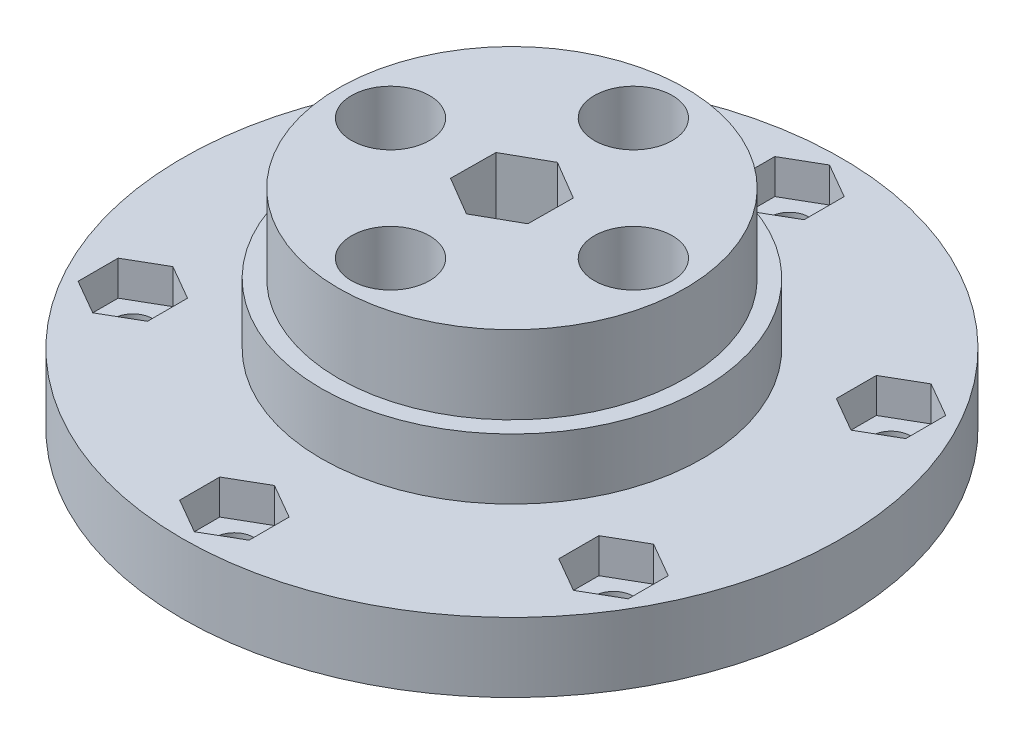
SolidWorks part; units mm, degrees
ref_plane "Спереди" through (0, 0, 0) normal (0, 0, 1) x (1, 0, 0)
ref_plane "Сверху" through (0, 0, 0) normal (0, 1, 0) x (1, 0, 0)
ref_plane "Справа" through (0, 0, 0) normal (1, 0, 0) x (0, 0, -1)
sketch "Эскиз1" plane through (0, 0, 0) normal (0, 1, 0) x (1, 0, 0)
  circle A0 centre (0, 0) radius 38
  dimension "D1" = 76
extrude "Бобышка-Вытянуть1" add sketch "Эскиз1" along normal blind 8
sketch "Эскиз2" plane through (0, 8, 0) normal (0, 1, 0) x (1, 0, 0)
  circle A0 centre (0, 0) radius 20
  dimension "D1" = 40
extrude "Бобышка-Вытянуть2" add sketch "Эскиз2" along normal blind 16
sketch "Эскиз7" plane through (0, 8, 0) normal (0, 1, 0) x (1, 0, 0)
  circle A0 centre (0, 0) radius 22
  dimension "D1" = 44
extrude "Бобышка-Вытянуть3" add sketch "Эскиз7" along normal blind 7
sketch "Эскиз3" plane through (0, 24, 0) normal (0, 1, 0) x (1, 0, 0)
  circle A0 centre (0, 14) radius 4.5
  circle A1 centre (14, 0) radius 4.5
  circle A2 centre (0, -14) radius 4.5
  circle A3 centre (-14, 0) radius 4.5
  circle A4 centre (0, 0) radius 3.25
  point P12 (0, 0)
  dimension "D2" = 9
  dimension "D4" = 6.5
  dimension "D1" = 14
  dimension "D3" = 4
extrude "Вырез-Вытянуть1" cut sketch "Эскиз3" against normal through all
sketch "Эскиз4" plane through (0, 24, 0) normal (0, 1, 0) x (1, 0, 0)
  line L1 (4.4756, -2.6398) -> (4.524, 2.5561)
  line L2 (4.524, 2.5561) -> (0.0483, 5.1959)
  line L3 (0.0483, 5.1959) -> (-4.4756, 2.6398)
  line L4 (-4.4756, 2.6398) -> (-4.524, -2.5561)
  line L5 (-4.524, -2.5561) -> (-0.0483, -5.1959)
  line L6 (-0.0483, -5.1959) -> (4.4756, -2.6398)
  circle A0 centre (0, 0) radius 4.5 construction
  dimension "D1" = 9
extrude "Вырез-Вытянуть2" cut sketch "Эскиз4" against normal blind 12
sketch "Эскиз5" plane through (0, 24, 0) normal (0, 1, 0) x (1, 0, 0)
  circle A1 centre (0, 32) radius 2.25
  circle A2 centre (27.7128, 16) radius 2.25
  circle A3 centre (27.7128, -16) radius 2.25
  circle A4 centre (0, -32) radius 2.25
  circle A5 centre (-27.7128, -16) radius 2.25
  circle A6 centre (-27.7128, 16) radius 2.25
  point P17 (0, 0)
  dimension "D1" = 4.5
  dimension "D3" = 6
  dimension "D2" = 32
extrude "Вырез-Вытянуть3" cut sketch "Эскиз5" against normal through all
sketch "Эскиз6" plane through (0, 8, 0) normal (0, 1, 0) x (1, 0, 0)
  line L0 (27.7128, 11.3812) -> (31.7128, 13.6906)
  line L1 (4, 29.6906) -> (4, 34.3094)
  line L2 (4, 34.3094) -> (0, 36.6188)
  line L3 (0, 36.6188) -> (-4, 34.3094)
  line L4 (-4, 34.3094) -> (-4, 29.6906)
  line L5 (-4, 29.6906) -> (0, 27.3812)
  line L6 (0, 27.3812) -> (4, 29.6906)
  line L7 (31.7128, 13.6906) -> (31.7128, 18.3094)
  line L8 (31.7128, 18.3094) -> (27.7128, 20.6188)
  line L9 (27.7128, 20.6188) -> (23.7128, 18.3094)
  line L10 (23.7128, 18.3094) -> (23.7128, 13.6906)
  line L11 (23.7128, 13.6906) -> (27.7128, 11.3812)
  line L12 (23.7128, -18.3094) -> (27.7128, -20.6188)
  line L13 (27.7128, -20.6188) -> (31.7128, -18.3094)
  line L14 (31.7128, -18.3094) -> (31.7128, -13.6906)
  line L15 (31.7128, -13.6906) -> (27.7128, -11.3812)
  line L16 (27.7128, -11.3812) -> (23.7128, -13.6906)
  line L17 (23.7128, -13.6906) -> (23.7128, -18.3094)
  line L18 (-4, -29.6906) -> (-4, -34.3094)
  line L19 (-4, -34.3094) -> (0, -36.6188)
  line L20 (0, -36.6188) -> (4, -34.3094)
  line L21 (4, -34.3094) -> (4, -29.6906)
  line L22 (4, -29.6906) -> (0, -27.3812)
  line L23 (0, -27.3812) -> (-4, -29.6906)
  line L24 (-27.7128, -11.3812) -> (-31.7128, -13.6906)
  line L25 (-31.7128, -13.6906) -> (-31.7128, -18.3094)
  line L26 (-31.7128, -18.3094) -> (-27.7128, -20.6188)
  line L27 (-27.7128, -20.6188) -> (-23.7128, -18.3094)
  line L28 (-23.7128, -18.3094) -> (-23.7128, -13.6906)
  line L29 (-23.7128, -13.6906) -> (-27.7128, -11.3812)
  line L30 (-23.7128, 18.3094) -> (-27.7128, 20.6188)
  line L31 (-27.7128, 20.6188) -> (-31.7128, 18.3094)
  line L32 (-31.7128, 18.3094) -> (-31.7128, 13.6906)
  line L33 (-31.7128, 13.6906) -> (-27.7128, 11.3812)
  line L34 (-27.7128, 11.3812) -> (-23.7128, 13.6906)
  line L35 (-23.7128, 13.6906) -> (-23.7128, 18.3094)
  circle A0 centre (0, 32) radius 4 construction
  circle A1 centre (27.7128, 16) radius 4 construction
  circle A2 centre (27.7128, -16) radius 4 construction
  circle A3 centre (0, -32) radius 4 construction
  circle A4 centre (-27.7128, -16) radius 4 construction
  circle A5 centre (-27.7128, 16) radius 4 construction
  point P52 (0, 0)
  dimension "D1" = 8
  dimension "D2" = 6
extrude "Вырез-Вытянуть4" cut sketch "Эскиз6" against normal blind 4
chamfer "Фаска1" [suppressed] distance 0.5 angle 45
